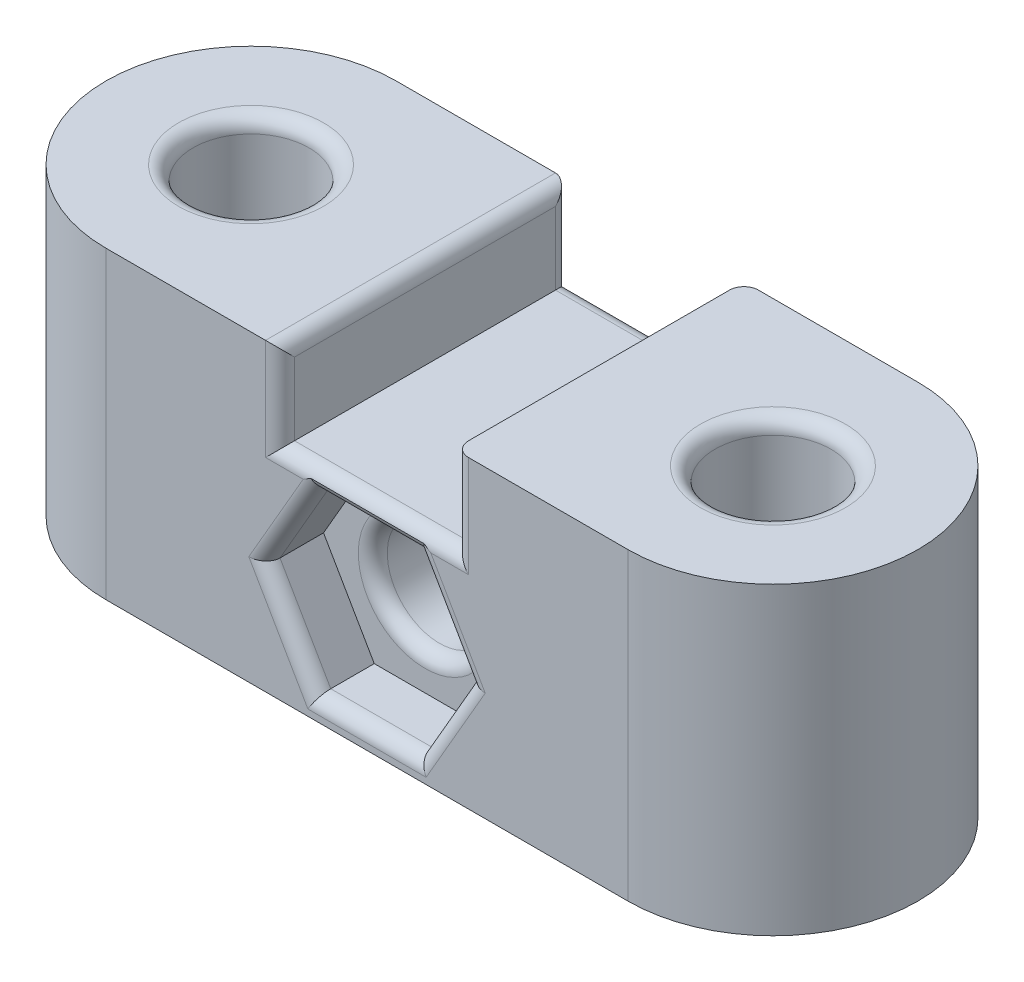
SolidWorks part; units mm, degrees
ref_plane "Front Plane" through (0, 0, 0) normal (0, 0, 1) x (1, 0, 0)
ref_plane "Top Plane" through (0, 0, 0) normal (0, 1, 0) x (1, 0, 0)
ref_plane "Right Plane" through (0, 0, 0) normal (1, 0, 0) x (0, 0, -1)
sketch "Belt Clamp" plane through (0, 0, 0) normal (0, 1, 0) x (1, 0, 0)
  line L1 (-18, 10) -> (0, 10)
  line L3 (-18, 0) -> (0, 0)
  arc A0 (-18, 10) -> (-18, 0) centre (-18, 5) ccw
  arc A1 (0, 0) -> (0, 10) centre (0, 5) ccw
  dimension "D1" = 18
  dimension "D2" = 10
extrude "Boss-Extrude2" add sketch "Belt Clamp" along normal blind 10.5
sketch "Screw Holes" plane through (0, 0, 0) normal (0, -1, 0) x (1, 0, 0)
  circle A0 centre (0, -5) radius 2
  circle A1 centre (-18, -5) radius 2
  dimension "D1" = 4
extrude "Cut-Extrude1" cut sketch "Screw Holes" against normal up to surface (10.5 mm away) up to face at (-9, 10.5, -5)
fillet "Fillet1" radius 0.5 4 edges at (0, 10.5, -3) (-18, 10.5, -3) (0, 0, -7) (-18, 0, -7)
sketch "Belt Opening" plane through (0, 10.5, 0) normal (0, 1, 0) x (1, 0, 0)
  line L2 (5, 5) -> (-23, 5) construction
  line L3 (-9, 0) -> (-9, 10) construction
  line L4 (-18, 0) -> (0, 0) construction
  line L5 (0, 10) -> (-18, 10) construction
  line L8 (-6, 0) -> (-12, 0)
  line L9 (-6, 0) -> (-6, 10)
  line L10 (-6, 10) -> (-12, 10)
  line L11 (-12, 0) -> (-12, 10)
  line L12 (-6, 0) -> (-12, 10) construction
  line L13 (-6, 10) -> (-12, 0) construction
  arc A0 (0, 0) -> (0, 10) centre (0, 5) ccw construction
  arc A1 (-18, 10) -> (-18, 0) centre (-18, 5) ccw construction
  point P15 (-9, 5)
  dimension "D1" = 6
extrude "Cut-Extrude2" cut sketch "Belt Opening" against normal blind 3
sketch "Hex Nut" plane through (0, 0, 0) normal (0, 0, 1) x (1, 0, 0)
  line L0 (-9, 0) -> (-9, 7.5) construction
  line L1 (-18, 0) -> (0, 0) construction
  line L2 (-12, 7.5) -> (-6, 7.5) construction
  line L3 (-9, 7.5) -> (-9, 3.75) construction
  line L4 (-9, 3.75) -> (-23, 3.75) construction
  line L5 (-23, 10.5) -> (-23, 0) construction
  line L6 (-23, 3.75) -> (5, 3.75) construction
  line L9 (5, 0) -> (5, 10.5) construction
  line L12 (-12.5, 3.75) -> (-10.75, 0.7189)
  line L13 (-10.75, 0.7189) -> (-7.25, 0.7189)
  line L14 (-7.25, 0.7189) -> (-5.5, 3.75)
  line L15 (-5.5, 3.75) -> (-7.25, 6.7811)
  line L16 (-7.25, 6.7811) -> (-10.75, 6.7811)
  line L17 (-10.75, 6.7811) -> (-12.5, 3.75)
  circle A0 centre (-9, 3.75) radius 3.0311 construction
  dimension "D1" = 7
extrude "Cut-Extrude3" cut sketch "Hex Nut" against normal blind 2
sketch "Stretcher Hole" plane through (0, 0, -2) normal (0, 0, 1) x (1, 0, 0)
  line L0 (-12.5, 3.75) -> (-5.5, 3.75) construction
  circle A0 centre (-9, 3.75) radius 1.8
  dimension "D1" = 3.6
extrude "Cut-Extrude4" cut sketch "Stretcher Hole" against normal up to surface (8 mm away) up to face at (-9, 7.125, -10)
fillet "Fillet2" radius 0.5 2 edges at (-7.2, 3.75, -2) (-7.2, 3.75, -10)
fillet "Fillet3" radius 0.5 6 edges at (-6.375, 2.2345, 0) (-6.375, 5.2655, 0) (-9, 6.7811, 0) (-11.625, 5.2655, 0) (-11.625, 2.2345, 0) (-9, 0.7189, 0)
fillet "Fillet8" radius 0.5 6 edges at (-12, 9, 0) (-6, 9, 0) (-12, 10.5, -5) (-12, 9, -10) (-9, 7.5, -10) (-6, 9, -10)
fillet "Fillet9" radius 0.5 1 edges at (-9, 7.5, 0)
